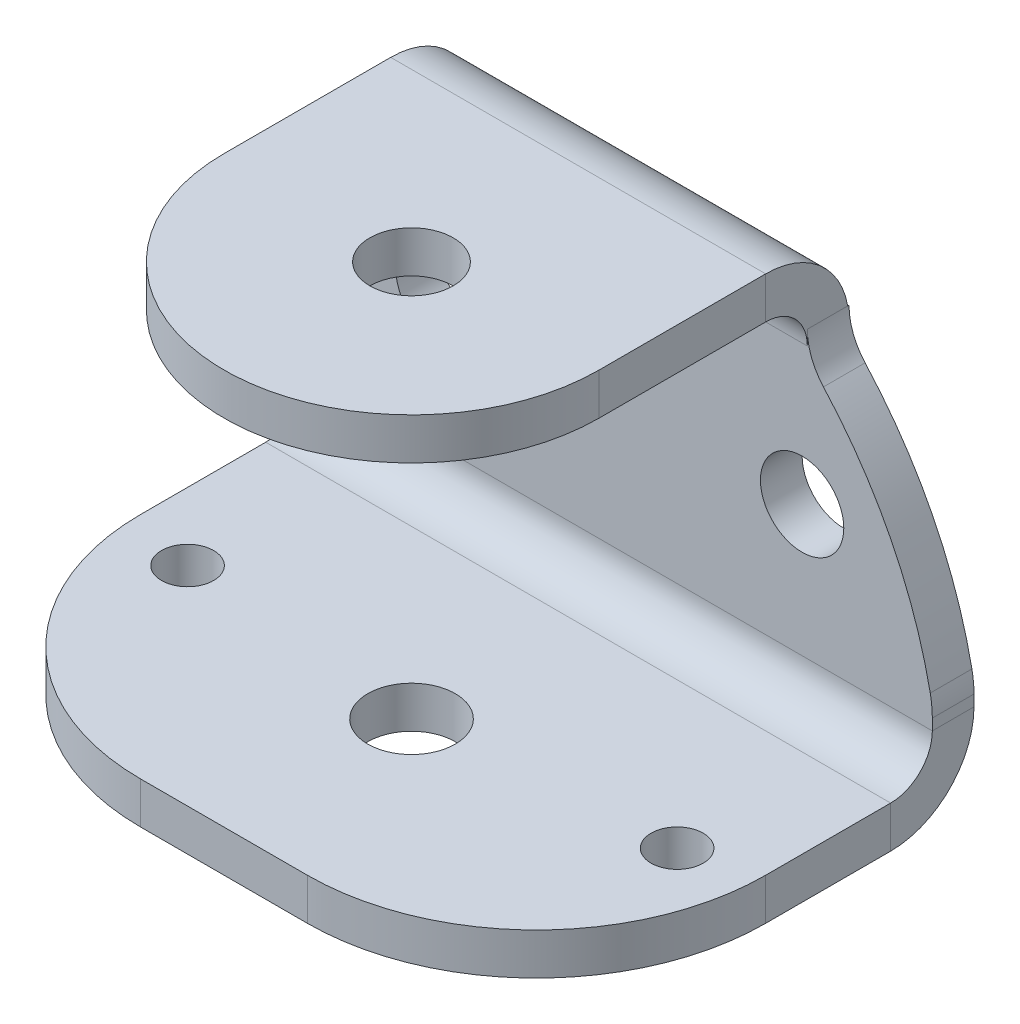
SolidWorks part; units mm, degrees
note: The reader was unsure of these and kept them because the rebuilt part matched: flange length of "Brida de arista1", "Brida de arista2".
material "acero"
ref_plane "Alzado" through (0, 0, 0) normal (0, 0, 1) x (1, 0, 0)
ref_plane "Planta" through (0, 0, 0) normal (0, 1, 0) x (1, 0, 0)
ref_plane "Vista lateral" through (0, 0, 0) normal (1, 0, 0) x (0, 0, -1)
sketch "Croquis1" plane through (0, 0, 0) normal (0, 0, 1) x (1, 0, 0)
  line L0 (0, 0) -> (30, 0)
  line L1 (30, 0) -> (30, 3)
  line L2 (24, 17) -> (6, 17)
  line L3 (6, 17) -> (6, 14.5)
  line L4 (15, 0) -> (15, 17) construction
  line L5 (30, 3) -> (24, 14.5) construction
  line L6 (0.1196, 5.3911) -> (4.2909, 13.386) construction
  line L8 (6, 14.5) -> (0, 3) construction
  line L9 (0, 3) -> (0, 0)
  line L10 (24, 14.5) -> (24, 17)
  arc A0 (0, 3) -> (6, 14.5) centre (21.2027, -0.7471) cw
  arc A1 (30, 3) -> (24, 14.5) centre (8.7973, -0.7471) ccw
  dimension "D1" = 30
  dimension "D2" = 17
  dimension "D3" = 18
  dimension "D4" = 3
  dimension "D5" = 2.5
  dimension "D6" = 1
base flange "Brida base1" sketch "Croquis1" thickness 2 reverse thickness direction no parameters "D1"=0.7366
fillet "Redondeo5mm" radius 5 2 edges at (30, 3, -1) (0, 3, -1)
fillet "Redondeo3mm" radius 3 2 edges at (24, 14.5, -1) (6, 14.5, -1)
edge flange "Brida de arista1" sketch "Croquis8" flange angle 90 flange length 19 flange position material outside bend radius 2 thickness 2 relief rectangular parameters "D6"=10
sketch "Croquis8" plane through (0, 0, 0) normal (0, -1, 0) x (1, 0, 0)
  line L0 (0, 0) -> (30, 0) construction
  line L1 (0, 0) -> (30, 0)
  line L2 (0, 0) -> (0, 19)
  line L3 (0, 19) -> (30, 19)
  line L4 (30, 19) -> (30, 0)
  dimension "D1" = 19
bend "Pliegue de arista5" bend radius 2 bend angle 90 parameters "D5"=1
edge flange "Brida de arista2" sketch "Croquis11" flange angle 90 flange length 10 flange position material outside bend radius 2 thickness 2 relief none parameters "D6"=10
sketch "Croquis11" plane through (0, 17, 0) normal (0, 1, 0) x (-1, 0, 0)
  line L0 (-24, 0) -> (-6, 0) construction
  line L1 (-24, 0) -> (-6, 0)
  line L2 (-24, 0) -> (-24, 10)
  line L4 (-6, 10) -> (-6, 0)
  arc A0 (-6, 10) -> (-24, 10) centre (-15, 10) ccw
bend "Pliegue de arista2" bend radius 2 bend angle 90 parameters "D5"=2
sketch "Croquis26" plane through (0, 0, -2) normal (0, 0, -1) x (-1, 0, 0)
  line L0 (-15, 15) -> (-15, 2) construction
  line L1 (-24, 15) -> (-6, 15) construction
  line L2 (-6.25, 8.3) -> (-15, 8.3) construction
  line L3 (-30, 2) -> (0, 2) construction
  line L4 (-30, 0) -> (0, 0) construction
  circle A1 centre (-6.25, 8.3) radius 2
  circle A2 centre (-23.75, 8.3) radius 2
  dimension "D1" = 4
  dimension "D3" = 8.3
  dimension "D2" = 17.5
extrude "Cortar-Extruir6" cut sketch "Croquis26" against normal up to next normal cut yes
fillet "Redondeo11mm" radius 11 2 edges at (0, -1, 19) (30, -1, 19)
hole_wizard "Taladro roscado M32" positions "Croquis33" profile "Croquis32" tap size "M3" standard "Iso"
sketch "Croquis33" plane through (0, 0, 0) normal (0, 1, 0) x (1, 0, 0)
  line L1 (15, 2) -> (15, -22.7453) construction
  line L2 (24, 2) -> (6, 2) construction
  line L3 (30, 0) -> (0, 0) construction
  point P0 (3.25, -9)
  point P2 (26.75, -9)
  dimension "D1" = 9
  dimension "D2" = 11.75
sketch "Croquis32" plane through (3.25, 0, 9) normal (1, 0, 0) x (0, 0, 1)
  line L0 (0, 0) -> (0, 21.4011)
  line L1 (0, 21.4011) -> (1.25, 20.65)
  line L2 (1.25, 20.65) -> (1.25, 0)
  line L5 (1.25, 0) -> (0, 0)
  line L10 (0, 21.4011) -> (-1.25, 20.65) construction
  line L11 (0, -6.35) -> (0, 107.95) construction
  dimension "Diámetro de perforador para roscar" = 2.5
  dimension "Profundidad de perforador para roscar" = 20.65
  dimension "Ángulo de perforador" = 118
cosmetic thread "Rosca de taladro5"
cosmetic thread "Rosca de taladro6"
hole_wizard "Taladro roscado M52" positions "Croquis35" profile "Croquis34" tap size "M5" standard "ISO" end condition up to next
sketch "Croquis35" plane through (3.7155, 0, 2.6381) normal (0, 1, 0) x (1, 0, 0)
  line L2 (20.2845, 4.6381) -> (2.2845, 4.6381) construction
  line L3 (11.2845, 4.6381) -> (11.2845, -10.5472) construction
  line L4 (26.2845, 2.6381) -> (-3.7155, 2.6381) construction
  point P0 (11.2845, -7.3619)
  dimension "D1" = 10
cosmetic thread "Rosca de taladro7"
sketch "Croquis34" plane through (15, 0, 10) normal (1, 0, 0) x (0, 0, 1)
  line L0 (0, 0) -> (0, 2)
  line L1 (0, 2) -> (2.1, 2)
  line L2 (2.1, 2) -> (2.1, 0)
  line L5 (2.1, 0) -> (0, 0)
  line L11 (0, -6.35) -> (0, 107.95) construction
  dimension "Diámetro de perforador para roscar hasta el siguiente" = 4.2
  dimension "Profundidad de perforador para roscar hasta el siguiente" = 2
sketch "Croquis36" plane through (0, 17, 0) normal (0, 1, 0) x (1, 0, 0)
  circle A0 centre (15, -10) radius 2
  circle A1 centre (15, -10) radius 2.1 construction
  dimension "D1" = 4
extrude "Cortar-Extruir7" cut sketch "Croquis36" along normal up to next normal cut yes
sketch "Líneas de pliegue1" [suppressed] plane through (0, 0, 0) normal (0, 1, 0) x (1, 0, 0)
sketch "Cuadro delimitador1" [suppressed] plane through (0, 0, 0) normal (0, 1, 0) x (1, 0, 0)
sheet metal parameters "Chapa metálica4" thickness 2 parameters "D1"=0.7366
flat pattern "Chapa desplegada4" [suppressed]
sketch "Líneas de pliegue2" plane through (0, 0, 0) normal (0, 1, 0) x (1, 0, 0)
sketch "Cuadro delimitador2" [suppressed] plane through (0, 0, 0) normal (0, 1, 0) x (1, 0, 0)
sheet metal parameters "Chapa metálica5" thickness 2 parameters "D1"=0.7366
flat pattern "Chapa desplegada4" [suppressed]
sketch "Líneas de pliegue2" plane through (0, 0, 0) normal (0, 1, 0) x (1, 0, 0)
sketch "Cuadro delimitador2" [suppressed] plane through (0, 0, 0) normal (0, 1, 0) x (1, 0, 0)
bend of the flat pattern "Aplanar-<Pliegue de arista5>1"
sheet metal parameters "Chapa metálica6" thickness 2 parameters "D1"=0.7366
flat pattern "Chapa desplegada4" [suppressed]
sketch "Líneas de pliegue2" plane through (0, 0, 0) normal (0, 1, 0) x (1, 0, 0)
sketch "Cuadro delimitador2" [suppressed] plane through (0, 0, 0) normal (0, 1, 0) x (1, 0, 0)
bend of the flat pattern "Aplanar-<Pliegue de arista2>1"
bend of the flat pattern "Aplanar-<Pliegue de arista5>2"
sheet metal parameters "Chapa metálica17" thickness 2 parameters "D1"=0.7366
flat pattern "Chapa desplegada4" [suppressed]
sketch "Líneas de pliegue3" plane through (0, 0, 0) normal (0, 1, 0) x (1, 0, 0)
sketch "Cuadro delimitador3" [suppressed] plane through (0, 0, 0) normal (0, 1, 0) x (1, 0, 0)
bend of the flat pattern "Aplanar-<Pliegue de arista5>6"
bend of the flat pattern "Aplanar-<Pliegue de arista2>2"
sheet metal parameters "Chapa metálica(19)" thickness 2 parameters "D1"=0.7366
flat pattern "Chapa desplegada4"
sketch "Líneas de pliegue3" plane through (0, 0, 0) normal (0, 0, 1) x (1, 0, 0)
sketch3d "Cuadro delimitador3" [suppressed]
  line L0 (30, -18.427, 0) -> (30, 36.427, 0) construction
  line L1 (0, -18.427, 0) -> (0, 36.427, 0) construction
  line L2 (30, -18.427, 0) -> (0, -18.427, 0) construction
  line L3 (30, 36.427, 0) -> (0, 36.427, 0) construction
bend of the flat pattern "Aplanar-<Pliegue de arista2>3"
bend of the flat pattern "Aplanar-<Pliegue de arista5>7"
sheet metal parameters "Chapa metálica(20)" thickness 2 parameters "D1"=0.7366
flat pattern "Chapa desplegada4"
sketch "Líneas de pliegue3" plane through (0, 0, 0) normal (0, 0, 1) x (1, 0, 0)
sketch3d "Cuadro delimitador3" [suppressed]
  line L0 (30, -18.427, 0) -> (30, 36.427, 0) construction
  line L1 (0, -18.427, 0) -> (0, 36.427, 0) construction
  line L2 (30, -18.427, 0) -> (0, -18.427, 0) construction
  line L3 (30, 36.427, 0) -> (0, 36.427, 0) construction
bend of the flat pattern "Aplanar-<Pliegue de arista2>3"
bend of the flat pattern "Aplanar-<Pliegue de arista5>7"
sheet metal parameters "Chapa metálica(21)" thickness 2 parameters "D1"=0.7366
flat pattern "Chapa desplegada4"
sketch "Líneas de pliegue3" plane through (0, 0, 0) normal (0, 0, 1) x (1, 0, 0)
  line L0 (24, 17.6781) -> (6, 17.6781) construction
  line L1 (0, -0.6781) -> (30, -0.6781) construction
  line L2 (24, 17.6781) -> (6, 17.6781) construction
  line L3 (0, -0.6781) -> (30, -0.6781) construction
sketch3d "Cuadro delimitador3" [suppressed]
  line L0 (24.214, 38.2888, 0) -> (24.214, -18.9235, 0) construction
  line L1 (-5.786, 38.2888, 0) -> (-5.786, -18.9235, 0) construction
  line L2 (24.214, 38.2888, 0) -> (-5.786, 38.2888, 0) construction
  line L3 (24.214, -18.9235, 0) -> (-5.786, -18.9235, 0) construction
bend of the flat pattern "Aplanar-<Pliegue de arista2>3"
bend of the flat pattern "Aplanar-<Pliegue de arista5>7"
